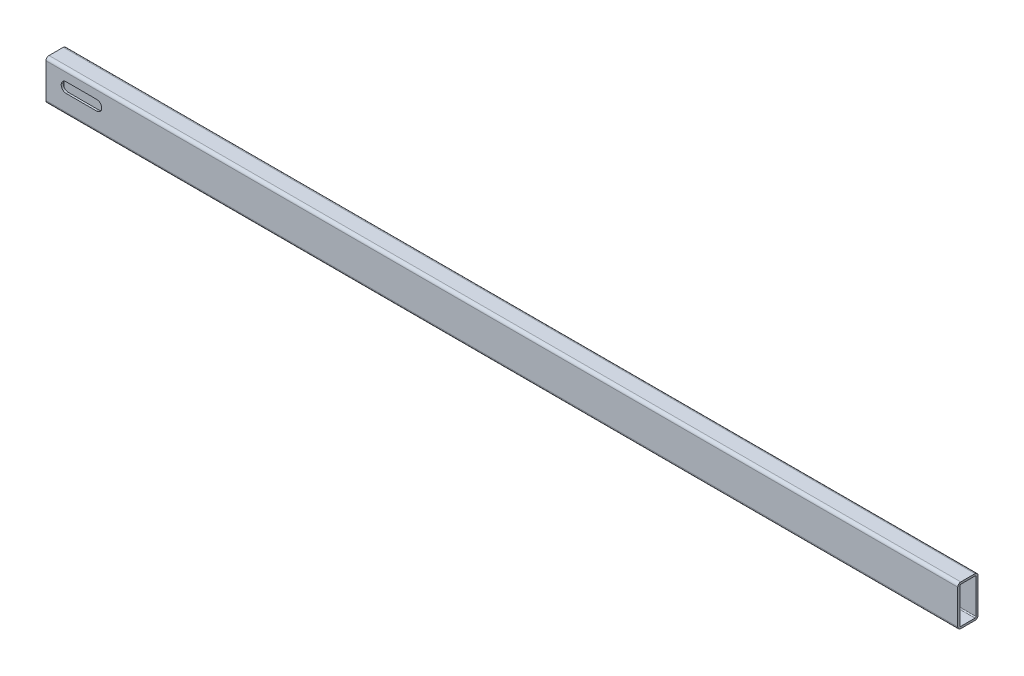
SolidWorks part; units mm, degrees
ref_plane "Спереди" through (0, 0, 0) normal (0, 0, 1) x (1, 0, 0)
ref_plane "Сверху" through (0, 0, 0) normal (0, 1, 0) x (1, 0, 0)
ref_plane "Справа" through (0, 0, 0) normal (1, 0, 0) x (0, 0, -1)
sketch "Эскиз1" plane through (0, 0, 0) normal (1, 0, 0) x (0, 0, -1)
  line L1 (1, 0) -> (15, 0)
  line L2 (0, 1) -> (0, 35)
  line L3 (1, 36) -> (15, 36)
  line L4 (16, 1) -> (16, 35)
  arc A4 (1, 0) -> (0, 1) centre (1, 1) cw
  arc A5 (15, 0) -> (16, 1) centre (15, 1) ccw
  arc A6 (16, 35) -> (15, 36) centre (15, 35) ccw
  arc A7 (0, 35) -> (1, 36) centre (1, 35) cw
  point P3 (0, 0)
  point P8 (0, 0)
  dimension "D1" = 1
extrude "Вытянуть-Тонкостенный1" add sketch "Эскиз1" along normal blind 900 thin thin type one direction wall 2
sketch "Эскиз2" plane through (0, 0, 2) normal (0, 0, 1) x (1, 0, 0)
  line L2 (20, 27) -> (50, 27)
  line L3 (20, 17) -> (50, 17)
  arc A0 (20, 17) -> (20, 27) centre (20, 22) cw
  arc A2 (50, 27) -> (50, 17) centre (50, 22) cw
  point P5 (0, 0)
  point P6 (0, 0)
  point P7 (0, 0)
  point P8 (0, 0)
  point P10 (0, 0)
extrude "Вырез-Вытянуть1" cut sketch "Эскиз2" against normal blind 40
